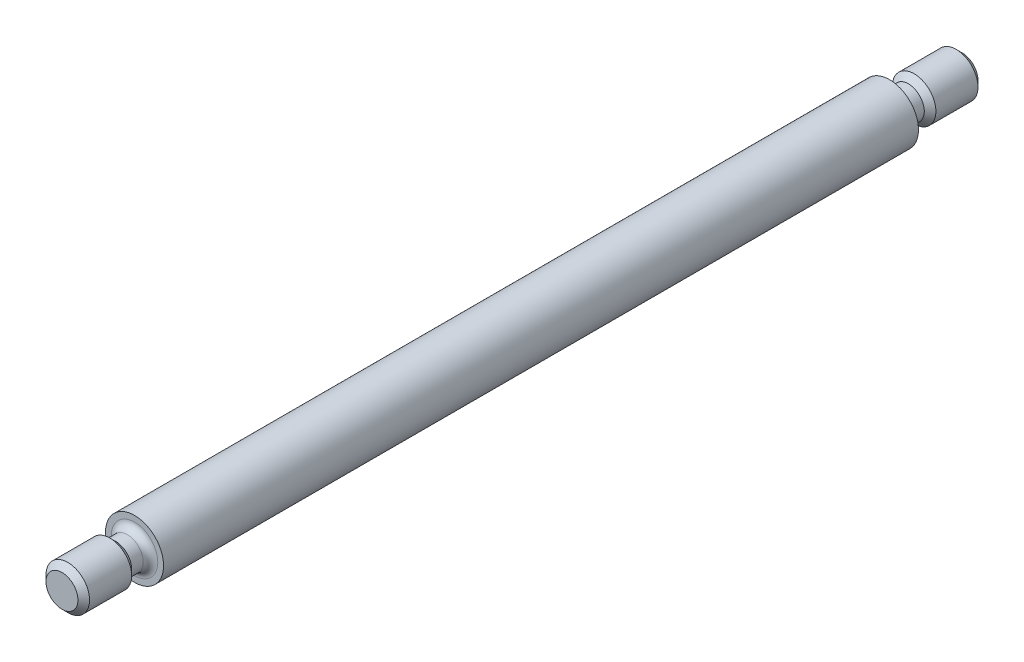
SolidWorks part; units mm, degrees
material "Простая углеродистая сталь"
ref_plane "Спереди" through (0, 0, 0) normal (0, 0, 1) x (1, 0, 0)
ref_plane "Сверху" through (0, 0, 0) normal (0, 1, 0) x (1, 0, 0)
ref_plane "Справа" through (0, 0, 0) normal (1, 0, 0) x (0, 0, -1)
sketch "Эскиз1" plane through (0, 0, 0) normal (0, 1, 0) x (1, 0, 0)
  line L0 (4.4008, 0) -> (7712.2053, 0) construction
  line L14 (0, 31) -> (-1.5, 31)
  line L15 (-1.5, 31) -> (-1.5, 27.3)
  line L17 (-2, 26) -> (-2, -26)
  line L19 (0, 60) -> (0, -49940) construction
  line L20 (-2, 26) -> (-1.1, 26)
  line L21 (-1.1, 26) -> (-1.1, 27.3)
  line L22 (-1.1, 27.3) -> (-1.5, 27.3)
  line L23 (-2, -26) -> (-1.1, -26)
  line L24 (-1.1, -27.3) -> (-1.5, -27.3)
  line L25 (-1.1, -26) -> (-1.1, -27.3)
  line L26 (-1.5, -31) -> (-1.5, -27.3)
  line L27 (0, -31) -> (-1.5, -31)
  line L28 (0, 31) -> (0, -31)
  point P7 (-2, 0)
  dimension "D1" = 26
  dimension "D2" = 31
  dimension "D3" = 0.5
  dimension "D4" = 2
  dimension "D5" = 1.1
  dimension "D6" = 1.3
revolve "Повернуть1" add sketch "Эскиз1" angle 360 about L28
chamfer "Фаска1" distance 0.4 angle 45 2 edges at (-1.5, 0, -31) (-1.5, 0, 31)
chamfer "Фаска2" distance 0.4 angle 45 2 edges at (-1.5, 0, -27.3) (-1.5, 0, 27.3)
fillet "Скругление1" radius 0.5 2 edges at (-1.1, 0, 26) (-1.1, 0, -26)
